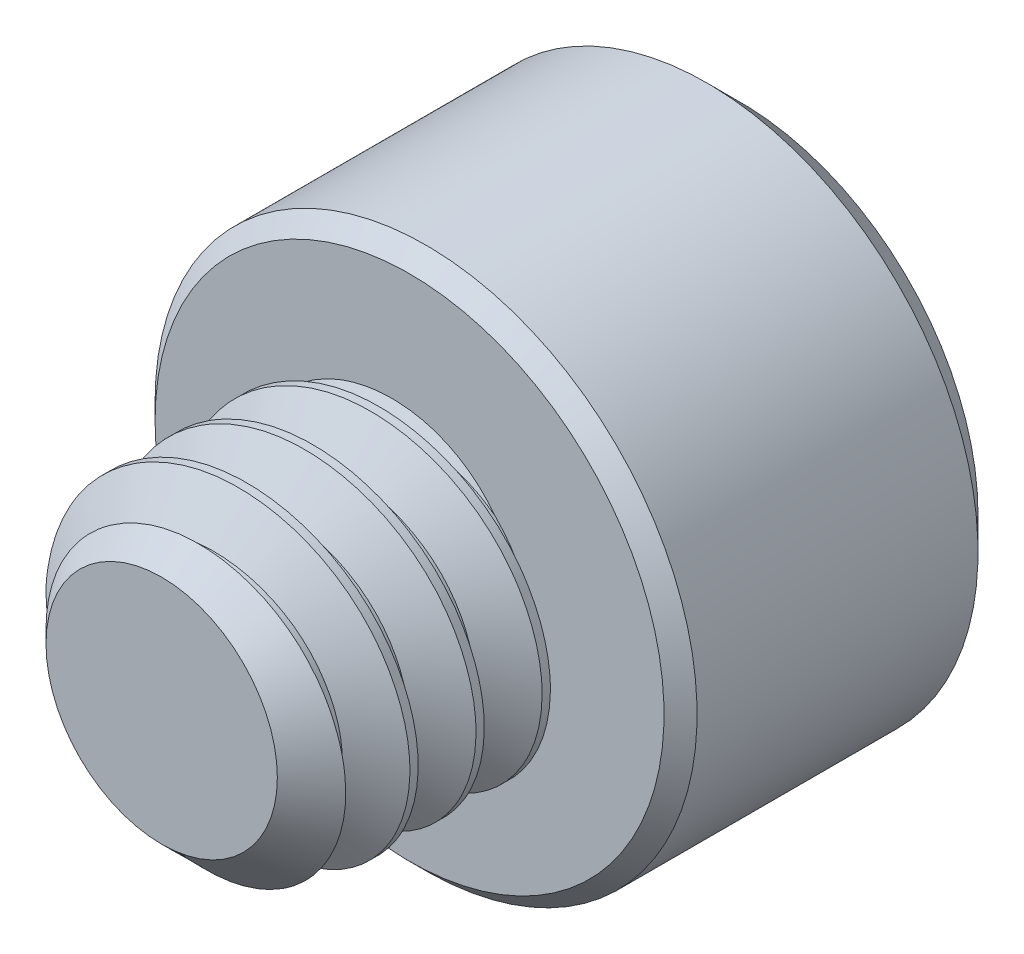
SolidWorks part; units mm, degrees
ref_plane "Front Plane" through (0, 0, 0) normal (0, 0, 1) x (1, 0, 0)
ref_plane "Top Plane" through (0, 0, 0) normal (0, 1, 0) x (1, 0, 0)
ref_plane "Right Plane" through (0, 0, 0) normal (1, 0, 0) x (0, 0, -1)
sketch "Sketch1" plane through (0, 0, 0) normal (0, 0, 1) x (1, 0, 0)
  line L0 (0, 1.5875) -> (0, -1.5875) construction
  circle A0 centre (0, 0) radius 1.5875
  dimension "OD" = 3.175
extrude "Extrude1" add sketch "Sketch1" against normal blind 2.3813
sketch "Sketch2" plane through (0, 0, 0) normal (0, 0, 1) x (1, 0, 0)
  circle A0 centre (0, 0) radius 1.5875 construction
  circle A1 centre (0, 0) radius 1.5875
curve "Helix/Spiral1" pitch 0.635 height 3.0163 radius 1.5875 centre (0, 0, 0) axis (0, 0, -1) start towards (0, 1, 0) parameters "pitch"=0.635
chamfer "Chamfer3" distance 0.4763 angle 45 1 edges at (1.5875, 0, 0)
sketch "Sketch3" plane through (0, 0, 0) normal (1, 0, 0) x (0, 0, -1)
  line L0 (-0.5556, 1.5875) -> (-0.3175, 1.1751)
  line L1 (-0.3175, 1.1751) -> (-0.2381, 1.1751)
  line L2 (-0.2381, 1.1751) -> (0, 1.5875)
  line L3 (-0.5556, 1.5875) -> (0, 1.5875)
  line L4 (-0.2778, 1.5875) -> (-0.2778, 1.1751) construction
  line L5 (-0.4366, 1.3813) -> (-0.1191, 1.3813) construction
  line L6 (0, 1.5875) -> (0, -1.5875) construction
  dimension "D2" = 0.3175
  dimension "D3" = 60
sweep "Cut-Sweep1" cut profiles "Sketch3" path "Helix/Spiral1" align with end faces yes
sketch "Sketch6" plane through (0, 0, -2.3813) normal (0, 0, -1) x (-1, 0, 0)
  circle A0 centre (0, 0) radius 2.6035
  dimension "head dia" = 5.207
extrude "Extrude2" add sketch "Sketch6" along normal blind 3.175
sketch "Sketch7" plane through (0, 0, -5.5563) normal (0, 0, -1) x (-1, 0, 0)
  line L1 (0, 1.3748) -> (-1.1906, 0.6874)
  line L2 (-1.1906, 0.6874) -> (-1.1906, -0.6874)
  line L3 (-1.1906, -0.6874) -> (0, -1.3748)
  line L4 (0, -1.3748) -> (1.1906, -0.6874)
  line L5 (1.1906, -0.6874) -> (1.1906, 0.6874)
  line L6 (1.1906, 0.6874) -> (0, 1.3748)
  circle A0 centre (0, 0) radius 1.1906 construction
  dimension "hex dia" = 2.3813
extrude "Cut-Extrude1" cut sketch "Sketch7" against normal blind 1.7859
sketch "Sketch8" plane through (0, 0, -5.5563) normal (0, 0, -1) x (-1, 0, 0)
  circle A0 centre (0, 0) radius 1.3748
extrude "Cut-Extrude2" cut sketch "Sketch8" against normal blind 0.3175 draft 45
chamfer "Chamfer1" distance 0.3175 angle 45 1 edges at (-2.6035, 0, -5.5563)
chamfer "Chamfer2" distance 0.1588 angle 45 1 edges at (-2.6035, 0, -2.3813)
equation "\"D3@Helix/Spiral1\" = \"screw length@Extrude1\"+\"pitch@Helix/Spiral1\""
equation "\"D1@Sketch3\" = \"pitch@Helix/Spiral1\"*.125"
equation "\"D2@Sketch3\" = \"pitch@Helix/Spiral1\"*.5"
equation "\"D1@Cut-Extrude1\" = \"hex dia@Sketch7\"*.75"
equation "\"D1@Chamfer1\" = \"head depth@Extrude2\"/10"
equation "\"D1@Sketch9\" = \"pitch@Helix/Spiral1\"*5.5"
equation "\"D1@Chamfer2\" = \"D1@Chamfer1\"/2"
equation "\"D1@Cut-Extrude2\" = \"D1@Chamfer2\"*2"
equation "\"D1@Chamfer3\" = \"pitch@Helix/Spiral1\"*.750"
equation "\"D2@Sketch9\" = \"head depth@Extrude2\""
equation "\"D3@Sketch9\" = \"head dia@Sketch6\""
equation "\"D4@Sketch9\" = \"screw length@Extrude1\""
